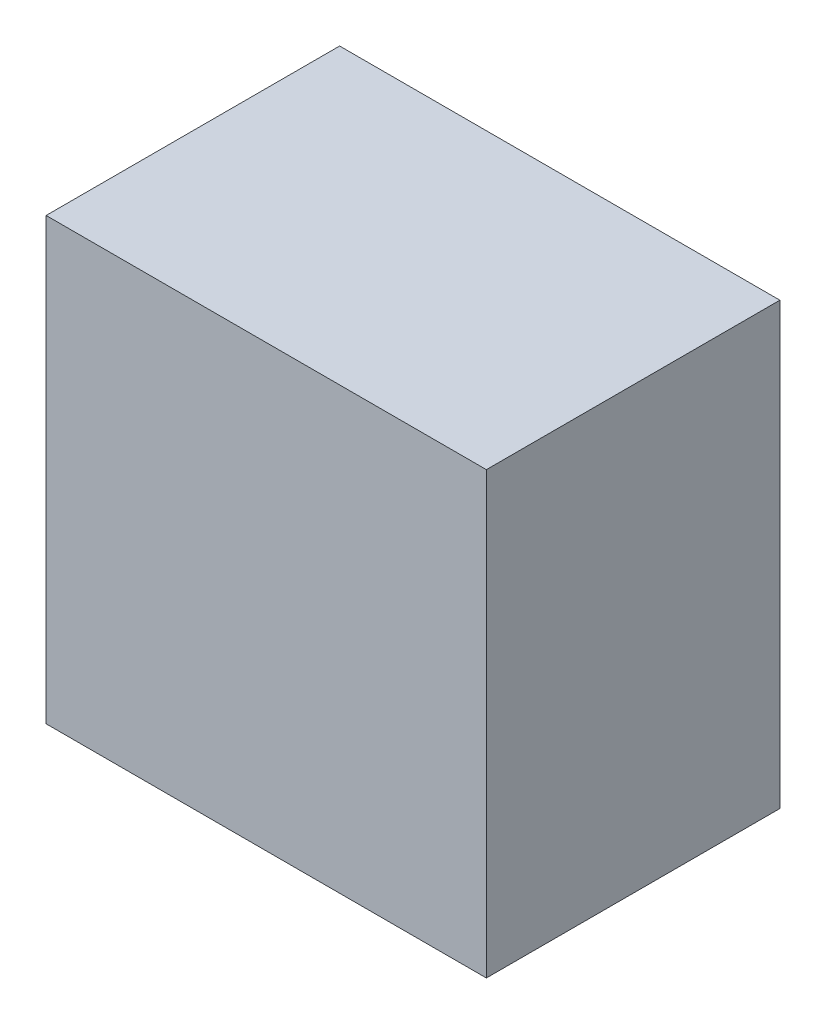
SolidWorks part; units mm, degrees
material "Custom Plastic"
ref_plane "Front Plane" through (0, 0, 0) normal (0, 0, 1) x (1, 0, 0)
ref_plane "Top Plane" through (0, 0, 0) normal (0, 1, 0) x (1, 0, 0)
ref_plane "Right Plane" through (0, 0, 0) normal (1, 0, 0) x (0, 0, -1)
other "Configuration Table"
sketch "Sketch1" plane through (0, 0, 0) normal (0, 0, 1) x (1, 0, 0)
  circle A0 centre (0, 0) radius 50
  dimension "D1" = 100
extrude "Boss-Extrude1" add sketch "Sketch1" along normal mid plane 50
sketch "Sketch2" plane through (0, 0, 0) normal (0, 0, 1) x (1, 0, 0)
  line L1 (-60, -60) -> (60, -60)
  line L2 (-60, -60) -> (-60, 60)
  line L3 (-60, 60) -> (60, 60)
  line L4 (60, -60) -> (60, 60)
  line L5 (-60, -60) -> (60, 60) construction
  line L6 (-60, 60) -> (60, -60) construction
  circle A0 centre (0, 0) radius 55
  dimension "D1" = 110
  dimension "D2" = 120
extrude "Boss-Extrude2" add sketch "Sketch2" along normal mid plane 60 separate body
sketch "Sketch3" plane through (0, 0, 30) normal (0, 0, 1) x (1, 0, 0)
  line L4 (60, -60) -> (60, 60)
  line L5 (60, 60) -> (-60, 60)
  line L6 (-60, 60) -> (-60, -60)
  line L7 (-60, -60) -> (60, -60)
  line L8 (60, -60) -> (60, 60)
  line L9 (60, 60) -> (-60, 60)
  line L10 (-60, 60) -> (-60, -60)
  line L11 (-60, -60) -> (60, -60)
  dimension "D1" = 0
extrude "Boss-Extrude3" add sketch "Sketch3" along normal blind 10
mirror "Mirror1" about plane through (0, 0, 0) normal (0, 0, 1) of "Boss-Extrude3"
